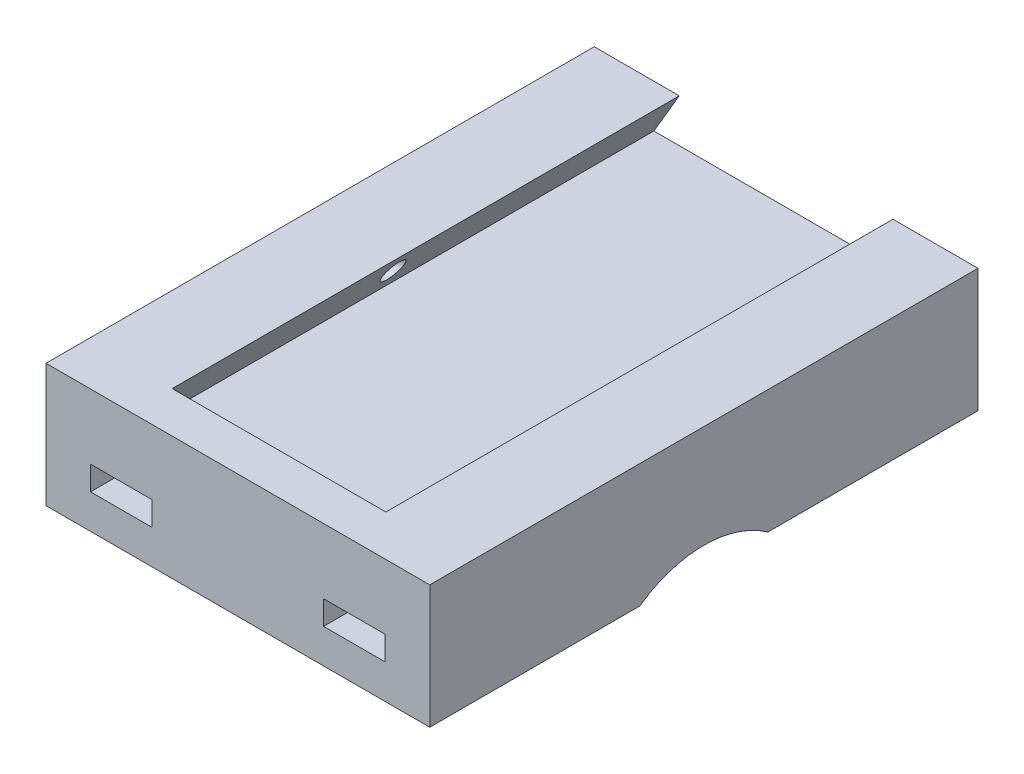
SolidWorks part; units mm, degrees
ref_plane "Front Plane" through (0, 0, 0) normal (0, 0, 1) x (1, 0, 0)
ref_plane "Top Plane" through (0, 0, 0) normal (0, 1, 0) x (1, 0, 0)
ref_plane "Right Plane" through (0, 0, 0) normal (1, 0, 0) x (0, 0, -1)
sketch "Sketch1" plane through (0, 0, 0) normal (0, 0, 1) x (1, 0, 0)
  line L0 (-28, 0) -> (28, 0)
  line L1 (28, 0) -> (28, 18)
  line L2 (28, 18) -> (-28, 18)
  line L3 (-28, 18) -> (-28, 0)
extrude "Bracket Block" add sketch "Sketch1" along normal mid plane 80
sketch "Sketch2" plane through (0, 0, 0) normal (0, 0, 1) x (1, 0, 0)
  line L0 (-15.3, 18.5) -> (15.3, 18.5)
  line L1 (15.3, 18.5) -> (19.3, 11.7)
  line L2 (19.3, 11.7) -> (-19.3, 11.7)
  line L3 (-19.3, 11.7) -> (-15.3, 18.5)
extrude "Dovetail Channel" cut sketch "Sketch2" against normal blind 41 and the other way blind 34
sketch "Sketch3" plane through (0, 0, 0) normal (1, 0, 0) x (0, 0, -1)
  circle A0 centre (0, -13) radius 16
extrude "Tube Saddle" cut sketch "Sketch3" against normal through all and the other way through all
sketch "Sketch4" plane through (0, 0, 0) normal (0, 0, 1) x (1, 0, 0)
  line L0 (-21.5, 5) -> (-12.5, 5)
  line L1 (-12.5, 5) -> (-12.5, 8.5)
  line L2 (-12.5, 8.5) -> (-21.5, 8.5)
  line L3 (-21.5, 8.5) -> (-21.5, 5)
  line L4 (12.5, 5) -> (21.5, 5)
  line L5 (21.5, 5) -> (21.5, 8.5)
  line L6 (21.5, 8.5) -> (12.5, 8.5)
  line L7 (12.5, 8.5) -> (12.5, 5)
extrude "Strap Slots" cut sketch "Sketch4" against normal through all and the other way through all
sketch "Sketch5" plane through (0, 0, 0) normal (1, 0, 0) x (0, 0, -1)
  circle A0 centre (0, 15) radius 1.65
extrude "Lock Screw Hole" cut sketch "Sketch5" against normal through all
equation "\"BrW\" = 56.0"
equation "\"BrL\" = 80.0"
equation "\"BrH\" = 18.0"
equation "\"RailW\" = 30.0"
equation "\"RailW2\" = 38.0"
equation "\"RailH\" = 6.0"
equation "\"Slide\" = 0.3"
equation "\"StopT\" = 6.0"
equation "\"TubeD\" = 32.0"
equation "\"SaddleD\" = 3.0"
equation "\"StrapX\" = 17.0"
equation "\"StrapW\" = 9.0"
equation "\"StrapT\" = 3.5"
equation "\"StrapY0\" = 5.0"
equation "\"LockY\" = 15.0"
equation "\"LockD\" = 3.3"
equation "\"D1@Bracket Block\" = \"BrL\""
